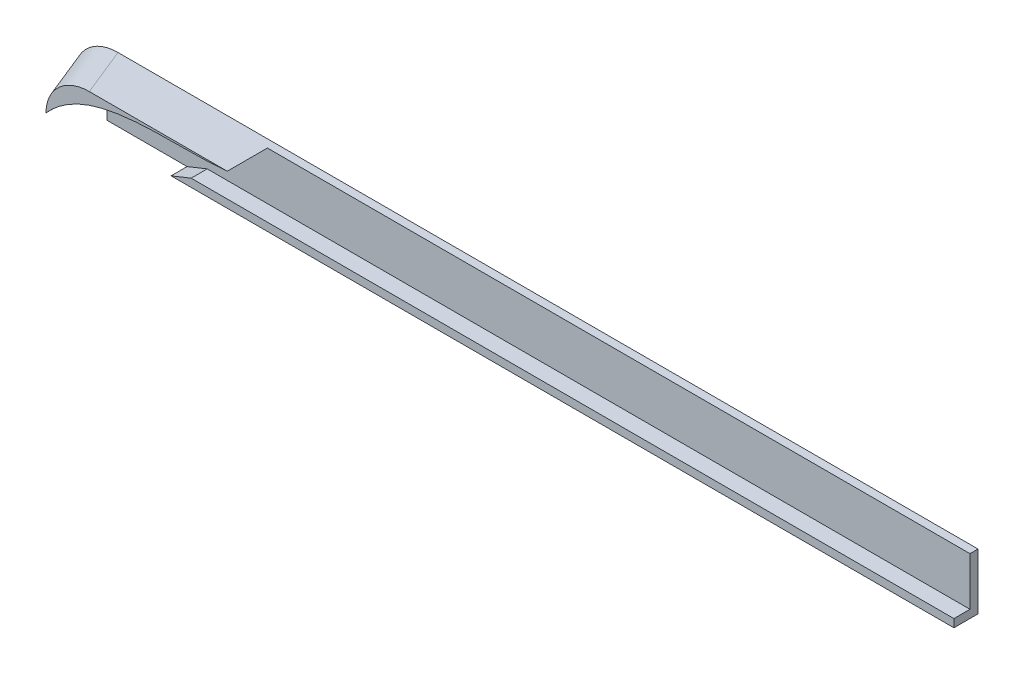
SolidWorks part; units mm, degrees
ref_plane "Płaszczyzna przednia" through (0, 0, 0) normal (0, 0, 1) x (1, 0, 0)
ref_plane "Płaszczyzna górna" through (0, 0, 0) normal (0, 1, 0) x (1, 0, 0)
ref_plane "Płaszczyzna prawa" through (0, 0, 0) normal (1, 0, 0) x (0, 0, -1)
sketch "Sketch1" plane through (0, 0, 0) normal (0, 0, 1) x (1, 0, 0)
  line L1 (-186.05, 8.825) -> (28.95, 8.825)
  line L2 (-186.05, 8.825) -> (-186.05, -5.175)
  line L3 (-186.05, -5.175) -> (28.95, -5.175)
  line L4 (28.95, 8.825) -> (28.95, -5.175)
  dimension "D1" = 14
  dimension "D2" = 215
extrude "Boss-Extrude1" add sketch "Sketch1" along normal blind 2
sketch "Sketch2" plane through (0, 0, 2) normal (0, 0, 1) x (1, 0, 0)
  line L0 (28.95, -5.175) -> (28.95, 8.825) construction
  line L1 (-186.05, -5.175) -> (28.95, -5.175)
  line L2 (-186.05, -5.175) -> (-186.05, -3.175)
  line L3 (-186.05, -3.175) -> (28.95, -3.175)
  line L4 (28.95, -5.175) -> (28.95, -3.175)
  dimension "D1" = 2
extrude "Boss-Extrude2" add sketch "Sketch2" along normal blind 4
sketch "Sketch3" plane through (0, 0, 0) normal (0, 0, -1) x (-1, 0, 0)
  line L0 (186.05, 8.825) -> (186.05, -1.175)
  line L1 (186.05, 8.825) -> (186.05, -5.175) construction
  line L2 (186.05, -1.175) -> (196.05, -1.175)
  line L3 (186.05, 8.825) -> (196.05, 8.825)
  line L4 (196.05, 8.825) -> (196.05, -1.175)
  dimension "D1" = 10
  dimension "D2" = 10
extrude "Boss-Extrude3" add sketch "Sketch3" against normal blind 2
sketch "Sketch4" plane through (0, 0, 6) normal (0, 0, 1) x (1, 0, 0)
  line L0 (-186.05, -3.175) -> (-161.05, -3.175)
  line L1 (28.95, -3.175) -> (-186.05, -3.175) construction
  line L2 (-161.05, -3.175) -> (-166.05, -5.175)
  line L3 (-186.05, -5.175) -> (28.95, -5.175) construction
  line L4 (-166.05, -5.175) -> (-186.05, -5.175)
  line L5 (-186.05, -5.175) -> (-186.05, -3.175)
  dimension "D1" = 25
  dimension "D2" = 20
extrude "Cut-Extrude1" cut sketch "Sketch4" against normal blind 4
sketch "Sketch5" plane through (28.95, 0, 0) normal (1, 0, 0) x (0, 0, -1)
  line L1 (-2, 8.825) -> (-12, 8.825)
  line L2 (-2, 8.825) -> (-2, -1.175)
  line L3 (-2, -1.175) -> (-12, -1.175)
  line L4 (-12, 8.825) -> (-12, -1.175)
  dimension "D1" = 10
  dimension "D2" = 10
extrude "Boss-Extrude4" add sketch "Sketch5" against normal blind 50 from offset 175 offset against normal yes
sketch "Sketch6" plane through (0, 8.825, 0) normal (0, 1, 0) x (1, 0, 0)
  line L0 (-196.05, 0) -> (-191.2017, -12)
  line L1 (-196.05, -12) -> (-146.05, -12) construction
  line L2 (-191.2017, -12) -> (-196.05, -12)
  line L3 (-196.05, -12) -> (-196.05, 0)
  line L4 (28.95, 0) -> (-196.05, 0) construction
  dimension "D1" = 68
extrude "Cut-Extrude2" cut sketch "Sketch6" against normal blind 50
fillet "Fillet1" radius 10 1 edges at (-193.6258, 8.825, 6)
sketch "Sketch7" plane through (0, 0, 12) normal (0, 0, 1) x (1, 0, 0)
  line L0 (-180.4163, 8.825) -> (-146.05, 8.825) construction
  line L1 (-146.05, -1.175) -> (-146.05, 8.825) construction
  line L2 (-191.2017, -1.175) -> (-146.05, -1.175)
  line L3 (-146.05, -1.175) -> (-146.05, 8.825)
  spline S0 degree 3 poles (-146.05, 8.825) (-160.7062, 7.3343) (-180.094, 11.3349) (-191.2017, -1.175) knots 0 0 0 0 1 1 1 1
  dimension "D1" = 0.5
  dimension "D2" = 17
  dimension "D3" = 38
  dimension "D4" = 4.5
extrude "Cut-Extrude3" cut sketch "Sketch7" against normal blind 10
